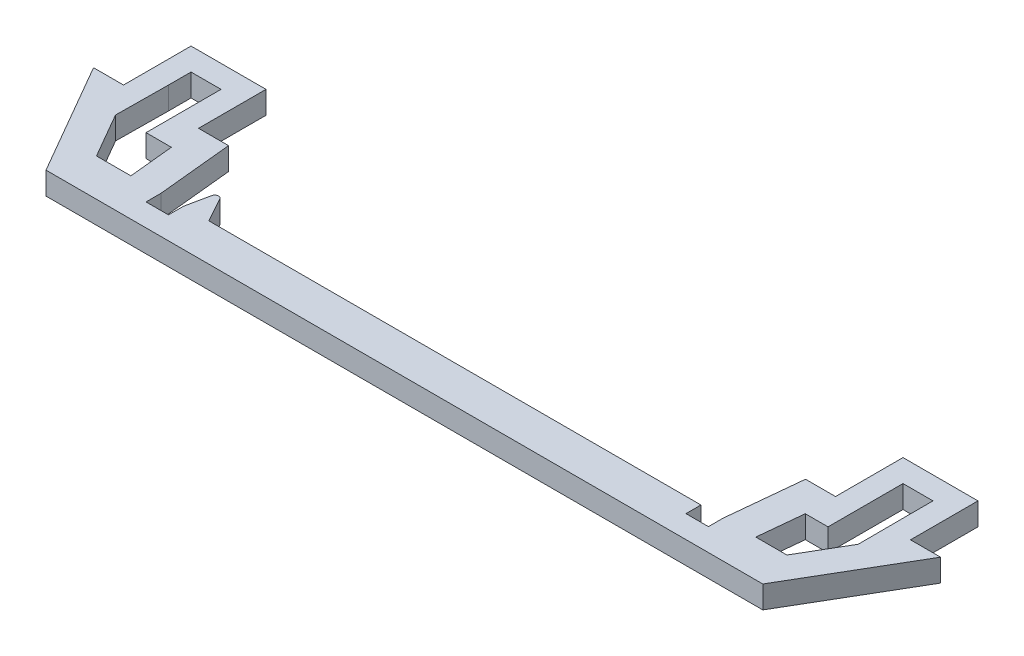
SolidWorks part; units mm, degrees
material "Custom Plastic"
ref_plane "Front Plane" through (0, 0, 0) normal (0, 0, 1) x (1, 0, 0)
ref_plane "Top Plane" through (0, 0, 0) normal (0, 1, 0) x (1, 0, 0)
ref_plane "Right Plane" through (0, 0, 0) normal (1, 0, 0) x (0, 0, -1)
sketch "Sketch1" plane through (0, 0, 0) normal (0, 1, 0) x (1, 0, 0)
  line L0 (-62.4186, -47.1587) -> (-58.4186, -47.1587)
  line L1 (-58.4186, -47.1587) -> (-58.4186, -38.1587)
  line L2 (-58.4186, -38.1587) -> (-48.4186, -38.1587)
  line L3 (-48.4186, -38.1587) -> (-48.4186, -47.1587)
  line L4 (-48.4186, -47.1587) -> (-44.4186, -47.1587)
  line L5 (-44.4186, -47.1587) -> (-43.4188, -57.1562)
  line L7 (31.5814, -57.2088) -> (32.5814, -47.2113)
  line L8 (32.5814, -47.2113) -> (36.5814, -47.2113)
  line L9 (36.5814, -47.2113) -> (36.5814, -38.2113)
  line L10 (36.5814, -38.2113) -> (46.5814, -38.2113)
  line L11 (46.5814, -38.2113) -> (46.5814, -47.2113)
  line L12 (46.5814, -47.2113) -> (50.5814, -47.2113)
  line L13 (50.5814, -47.2113) -> (41.8306, -62.1587)
  line L14 (41.8306, -62.1587) -> (-53.7583, -62.1587)
  line L15 (-53.7583, -62.1587) -> (-62.4186, -47.1587)
  line L16 (36.5478, -51.2113) -> (39.5814, -51.2113)
  line L17 (-55.4186, -41.1587) -> (-51.4186, -41.1587)
  line L18 (-55.4186, -41.1587) -> (-55.4186, -44.1587)
  line L20 (-51.4186, -41.1587) -> (-51.4186, -44.1587)
  line L21 (39.5814, -41.2113) -> (43.5814, -41.2113)
  line L22 (39.5814, -41.2113) -> (39.5814, -44.2113)
  line L24 (43.5814, -41.2113) -> (43.5814, -44.2113)
  line L25 (43.6046, -51.2113) -> (40.0934, -57.2088)
  line L26 (40.0934, -57.2088) -> (35.9479, -57.2088)
  line L27 (35.9479, -57.2088) -> (36.5478, -51.2113)
  line L28 (-51.4186, -51.1587) -> (-48.0385, -51.1587)
  line L29 (-48.0385, -51.1587) -> (-47.4385, -57.1587)
  line L30 (-47.4385, -57.1587) -> (-52.0263, -57.1587)
  line L31 (-52.0263, -57.1587) -> (-55.4904, -51.1587)
  line L32 (28.5814, -57.1587) -> (28.5814, -59.1587)
  line L33 (28.5814, -47.1587) -> (28.5814, -62.1587) construction
  line L34 (28.5814, -59.1587) -> (31.5814, -59.1587)
  line L35 (31.5814, -59.1587) -> (31.5814, -57.2088)
  line L36 (31.5814, -62.1587) -> (31.5814, -47.1587) construction
  line L38 (-43.4188, -57.1562) -> (-43.4188, -59.1587)
  line L39 (-43.4188, -59.1587) -> (-40.4188, -59.1587)
  line L40 (-40.4188, -59.1587) -> (-40.4188, -57.1587)
  line L41 (-37.0377, -57.1587) -> (28.5814, -57.1587)
  line L42 (-37.0377, -57.1587) -> (-38.8414, -53.9008)
  line L43 (43.5814, -44.2113) -> (43.6046, -51.2113)
  line L44 (-39.7683, -54.0409) -> (-40.4188, -57.1587)
  line L45 (39.5814, -44.2113) -> (39.5814, -51.2113)
  line L46 (-55.4186, -44.1587) -> (-55.4904, -51.1587)
  line L47 (-51.4186, -44.1587) -> (-51.4186, -51.1587)
  arc A0 (-39.7683, -54.0409) -> (-38.8414, -53.9008) centre (-39.2789, -54.143) cw
  dimension "D6" = 0.5
  dimension "D1" = 15
  dimension "D2" = 4
  dimension "D3" = 9
  dimension "D4" = 3
  dimension "D7" = 120
  dimension "D8" = 10
  dimension "D9" = 85
  dimension "D10" = 3
  dimension "D12" = 3
  dimension "D13" = 3
  dimension "D14" = 3
  dimension "D15" = 3
  dimension "D17" = 4
  dimension "D18" = 4
  dimension "D19" = 4
  dimension "D20" = 4
  dimension "D21" = 4
  dimension "D23" = 2
  dimension "D24" = 3
extrude "Boss-Extrude1" add sketch "Sketch1" along normal blind 3
